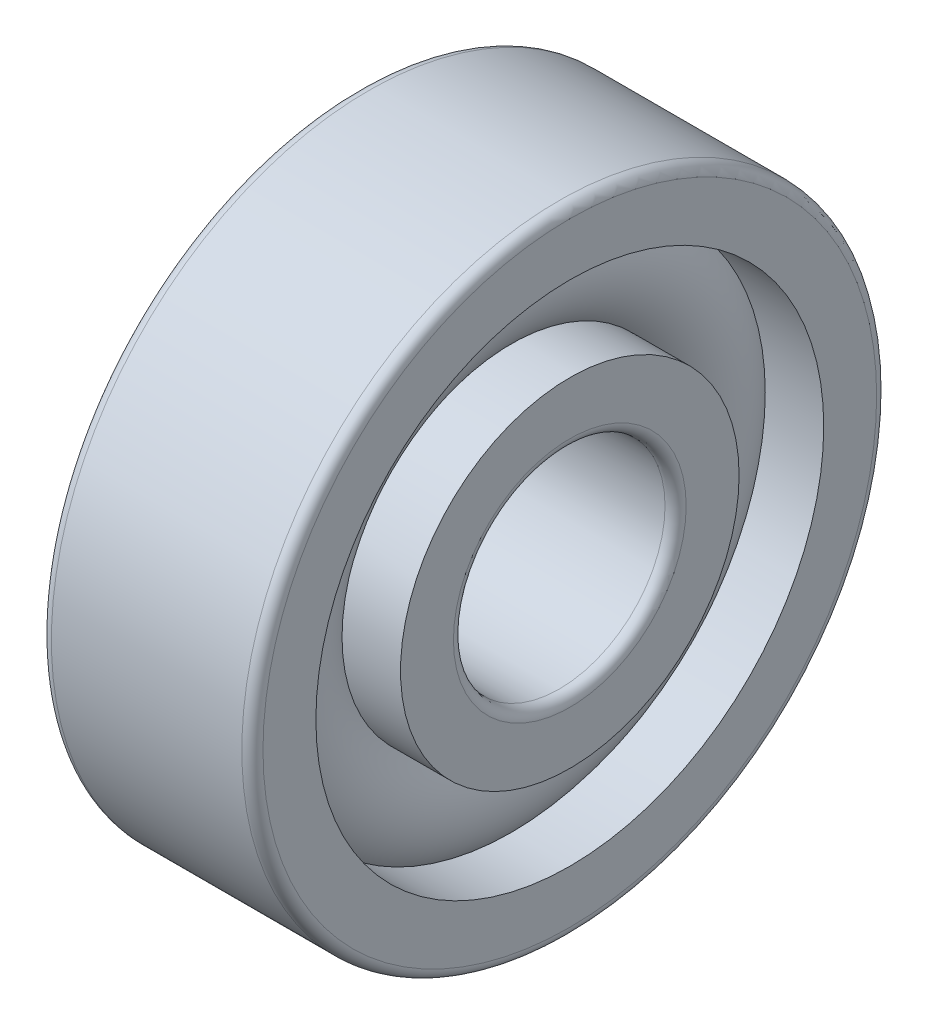
SolidWorks part; units mm, degrees
ref_plane "Plane1" through (0, 0, 0) normal (0, 0, 1) x (1, 0, 0)
ref_plane "Plane2" through (0, 0, 0) normal (0, 1, 0) x (1, 0, 0)
ref_plane "Plane3" through (0, 0, 0) normal (1, 0, 0) x (0, 0, -1)
sketch "Clipboard" plane through (0, 0, 0) normal (0, 0, 1) x (1, 0, 0)
  line L0 (-10, 0) -> (10, 0) construction
  line L1 (0, 0) -> (22.3471, -0.7804)
  line L2 (0, 0) -> (3.9976, 0.1396)
  line L3 (0, 0) -> (22.3471, -0.7804)
  line L4 (0, 0) -> (-22.3573, -0.3902)
  dimension "BallCLRad" = 4
sketch "CagSpiSke" plane through (0, 0, 0) normal (0, 0, 1) x (1, 0, 0)
  line L0 (0.12, 3.8) -> (0.12, 4.2)
  line L1 (0.12, 4.2) -> (-0.12, 4.2)
  line L2 (-0.12, 4.2) -> (-0.12, 3.8)
  line L3 (-0.12, 3.8) -> (0.12, 3.8)
  line L4 (-20.6375, 0) -> (20.6375, 0) construction
  line L5 (0, 0) -> (0, 23.7692) construction
  dimension "OD" = 8.4
  dimension "ID" = 7.6
revolve "CageSpine" add sketch "CagSpiSke" angle 0.001 about L4 reverse direction yes
ref_axis "Axis1" through (-50, 0, 0) along (1, 0, 0)
sketch "CagBalSke" plane through (0, 0, 0) normal (0, 0, 1) x (1, 0, 0)
  line L0 (-1.32, 4) -> (1.32, 4)
  line L1 (-1.905, 4) -> (1.905, 4) construction
  line L2 (-10, 0) -> (10, 0) construction
  line L3 (0, 0) -> (0, 24) construction
  arc A0 (1.32, 4) -> (-1.32, 4) centre (0, 4) cw
  dimension "BallCLRad" = 4
revolve "CageBall" [suppressed] add sketch "CagBalSke" angle 360 about L1 reverse direction yes
pattern_circular "CageBalls" [suppressed] count 2 every 180 about axis through (-50, 0, 0) along (1, 0, 0)
sketch "CagTrmODSke" plane through (0, 0, 0) normal (0, 0, 1) x (1, 0, 0)
  line L0 (1.321, 4.2) -> (1.321, 5.321)
  line L1 (1.321, 5.321) -> (-1.321, 5.321)
  line L2 (-1.321, 5.321) -> (-1.321, 4.2)
  line L3 (-1.321, 4.2) -> (1.321, 4.2)
  line L4 (-20.6375, 0) -> (20.6375, 0) construction
  line L5 (0, 0) -> (0, 25) construction
  dimension "Width" = 2.642
  dimension "ID" = 8.4
  dimension "OD" = 10.642
revolve "CageTrimOD" [suppressed] cut sketch "CagTrmODSke" angle 360 about L4 reverse direction yes
sketch "CagTrmIDSke" plane through (0, 0, 0) normal (0, 0, 1) x (1, 0, 0)
  line L0 (1.321, 2.681) -> (1.321, 3.8)
  line L1 (1.321, 3.8) -> (-1.321, 3.8)
  line L2 (-1.321, 3.8) -> (-1.321, 2.681)
  line L3 (-1.321, 2.681) -> (1.321, 2.681)
  line L4 (-20.6375, 0) -> (20.6375, 0) construction
  line L5 (0, 0) -> (0, 25) construction
  dimension "Width" = 2.642
  dimension "ID" = 5.362
  dimension "OD" = 7.6
revolve "CageTrimID" [suppressed] cut sketch "CagTrmIDSke" angle 360 about L4 reverse direction yes
sketch "BalSimSke" plane through (0, 0, 0) normal (0, 0, 1) x (1, 0, 0)
  line L0 (-10, 0) -> (10, 0) construction
  line L1 (-10, 4) -> (10, 4) construction
  line L2 (0, 0) -> (0, 23) construction
  circle A0 centre (0, 4) radius 1.2
  dimension "BallCLRad" = 4
  dimension "Ball_diameter" = 2.4
revolve "BallsSimplified" add sketch "BalSimSke" angle 360 about L0
sketch "BalDetSke" plane through (0, 0, 0) normal (0, 0, 1) x (1, 0, 0)
  line L0 (-1.2, 4) -> (1.2, 4)
  line L1 (-1.905, 4) -> (1.905, 4) construction
  line L2 (0, 0) -> (0, 25) construction
  arc A0 (1.2, 4) -> (-1.2, 4) centre (0, 4) cw
  dimension "BallCLRad" = 4
  dimension "Ball_diameter" = 2.4
revolve "BallDetailed" [suppressed] add sketch "BalDetSke" angle 360 about L1 reverse direction yes
sketch "InnRacSke" plane through (0, 0, 0) normal (0, 0, 1) x (1, 0, 0)
  line L0 (-0.8606, 3.2) -> (-2, 3.2)
  line L1 (-2, 3.2) -> (-2, 2.2)
  line L2 (-1.8, 2) -> (1.8, 2)
  line L3 (2, 2.2) -> (2, 3.2)
  line L4 (2, 3.2) -> (0.8606, 3.2)
  line L5 (-20.6375, 0) -> (20.6375, 0) construction
  line L6 (0, 0) -> (0, 30) construction
  arc A0 (-2, 2.2) -> (-1.8, 2) centre (-1.8, 2.2) ccw
  arc A1 (1.8, 2) -> (2, 2.2) centre (1.8, 2.2) ccw
  arc A2 (0.8606, 3.2) -> (-0.8606, 3.2) centre (0, 4) cw
  dimension "BallCLRad" = 4
  dimension "Fillet_radius" = 0.2
  dimension "Ball_diameter" = 2.35
  dimension "ID" = 4
  dimension "OD" = 6.4
  dimension "Width" = 4
revolve "InnerRace" add sketch "InnRacSke" angle 360 about L5 reverse direction yes
sketch "OutRacSke" plane through (0, 0, 0) normal (0, 0, 1) x (1, 0, 0)
  line L0 (-0.8606, 4.8) -> (-2, 4.8)
  line L1 (-2, 4.8) -> (-2, 5.8)
  line L2 (-1.8, 6) -> (1.8, 6)
  line L3 (2, 5.8) -> (2, 4.8)
  line L4 (2, 4.8) -> (0.8606, 4.8)
  line L5 (-20.6375, 0) -> (20.6375, 0) construction
  line L6 (0, 0) -> (0, 30) construction
  arc A0 (-2, 5.8) -> (-1.8, 6) centre (-1.8, 5.8) cw
  arc A1 (1.8, 6) -> (2, 5.8) centre (1.8, 5.8) cw
  arc A2 (0.8606, 4.8) -> (-0.8606, 4.8) centre (0, 4) ccw
  dimension "BallCLRad" = 4
  dimension "Fillet_radius" = 0.2
  dimension "Ball_diameter" = 2.35
  dimension "Width" = 4
revolve "OuterRace" add sketch "OutRacSke" angle 360 about L5 reverse direction yes
pattern_circular "BallsDetailed" [suppressed] count 2 every 180 about axis through (-50, 0, 0) along (1, 0, 0)
equation "\"BallCLRad@Clipboard\" = ( \"OD@OutRacSke\" + \"ID@InnRacSke\" ) / 4"
equation "\"BallCLRad@BalSimSke\" = \"BallCLRad@Clipboard\""
equation "\"BallCLRad@BalDetSke\" = \"BallCLRad@Clipboard\""
equation "\"BallCLRad@InnRacSke\" = \"BallCLRad@Clipboard\""
equation "\"BallCLRad@OutRacSke\" = \"BallCLRad@Clipboard\""
equation "\"Ball_diameter@InnRacSke\" = \"Ball_diameter@BalDetSke\" - 0.05"
equation "\"Ball_diameter@OutRacSke\" = \"Ball_diameter@BalDetSke\" - 0.05"
equation "\"Ball_diameter@BalSimSke\" = \"Ball_diameter@BalDetSke\""
equation "\"Width@OutRacSke\" = \"Width@InnRacSke\""
equation "\"Fillet_radius@OutRacSke\" = \"Fillet_radius@InnRacSke\""
equation "\"Max_count@Clipboard\" = int( 3.14159265 / atn(( \"Ball_diameter@BalDetSke\" / 2) / sqr( \"BallCLRad@Clipboard\"  *  \"BallCLRad@Clipboard\" - ( \"Ball_diameter@BalDetSke\" / 2) *  ( \"Ball_diameter@BalDetSke\" / 2))))"
equation "\"Max_count@Clipboard\" = ((sgn( \"Max_count@Clipboard\" - \"Count@Clipboard\" )-1)*( \"Max_count@Clipboard\" - \"Count@Clipboard\" ))/-2+ \"Count@Clipboard\""
equation "\"Count@BallsDetailed\" = int( \"Show_count@Clipboard\" ) "
equation "\"Count@BallsDetailed\" = ((sgn( \"Count@BallsDetailed\" - \"Max_count@Clipboard\" )-1)*( \"Count@BallsDetailed\" - \"Max_count@Clipboard\" ))/-2+ \"Max_count@Clipboard\""
equation "\"Count@BallsDetailed\" = ((sgn( \"Count@BallsDetailed\" - \"Min_count@Clipboard\" )+1)*( \"Count@BallsDetailed\" - \"Min_count@Clipboard\"))/2 +\"Min_count@Clipboard\""
equation "\"Angle@BallsDetailed\" = 360.0 / \"Max_count@Clipboard\""
equation "\"BallCLRad@CagBalSke\" = \"BallCLRad@Clipboard\""
equation "\"Count@CageBalls\" = \"Count@BallsDetailed\""
equation "\"Angle@CageBalls\" = \"Angle@BallsDetailed\""
equation "\"Angle@CageSpine\" =  \"Angle@CageBalls\" * ( \"Count@CageBalls\" -1 + int( \"Count@CageBalls\" / \"Max_count@Clipboard\" ) )  + 0.001 -  int( \"Count@CageBalls\" / \"Max_count@Clipboard\" ) * 0.001"
equation "\"Angle@CageSpine\" =  \"Angle@CageSpine\" * int( \"Min_count@Clipboard\" / 2) + int(1 / \"Min_count@Clipboard\")  * 0.001"
equation "\"CageWallOD@CagBalSke\" =  \"Ball_diameter@BalDetSke\" * 1.1"
equation "\"Thickness@CagSpiSke\" =  \"Ball_diameter@BalDetSke\" * 0.1"
equation "\"OD@CagTrmODSke\" = \"BallCLRad@Clipboard\" * 2 + \"CageWallOD@CagBalSke\" + 0.002"
equation "\"ID@CagTrmODSke\" = \"BallCLRad@Clipboard\" * 2 + \"Ball_diameter@BalDetSke\" / 6"
equation "\"OD@CagTrmIDSke\" = \"BallCLRad@Clipboard\" * 2 - \"Ball_diameter@BalDetSke\" / 6"
equation "\"ID@CagTrmIDSke\" = \"BallCLRad@Clipboard\" * 2 - \"CageWallOD@CagBalSke\" + 0.002"
equation "\"OD@CagSpiSke\" = \"ID@CagTrmODSke\""
equation "\"ID@CagSpiSke\" = \"OD@CagTrmIDSke\""
equation "\"Width@CagTrmODSke\" = \"CageWallOD@CagBalSke\" + 0.002"
equation "\"Width@CagTrmIDSke\" = \"CageWallOD@CagBalSke\" + 0.002"
